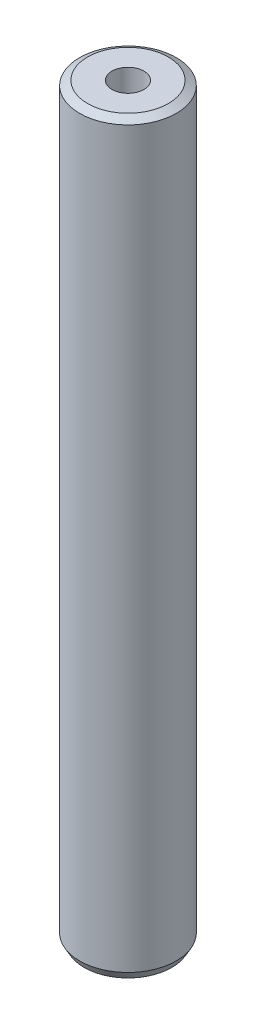
SolidWorks part; units mm, degrees
ref_plane "Front Plane" through (0, 0, 0) normal (0, 0, 1) x (1, 0, 0)
ref_plane "Top Plane" through (0, 0, 0) normal (0, 1, 0) x (1, 0, 0)
ref_plane "Right Plane" through (0, 0, 0) normal (1, 0, 0) x (0, 0, -1)
sketch "Sketch1" plane through (0, 0, 0) normal (0, 1, 0) x (1, 0, 0)
  circle A0 centre (0, 0) radius 35
  dimension "SHAFT_OD" = 70
extrude "Boss-Extrude1" add sketch "Sketch1" along normal blind 540.3558
sketch "Sketch2" plane through (0, 0, 0) normal (0, 1, 0) x (1, 0, 0)
  circle A0 centre (0, 0) radius 11.5556
  dimension "BORE_D" = 23.1113
extrude "Cut-Extrude1" cut sketch "Sketch2" along normal through all
chamfer "Chamfer1" distance 3.2563 angle 60.565 2 edges at (0, 540.3558, 35) (0, 0, 35) first distance on face at (0, 540.3558, 35) first distance on face at (0, 0, 11.5556)
